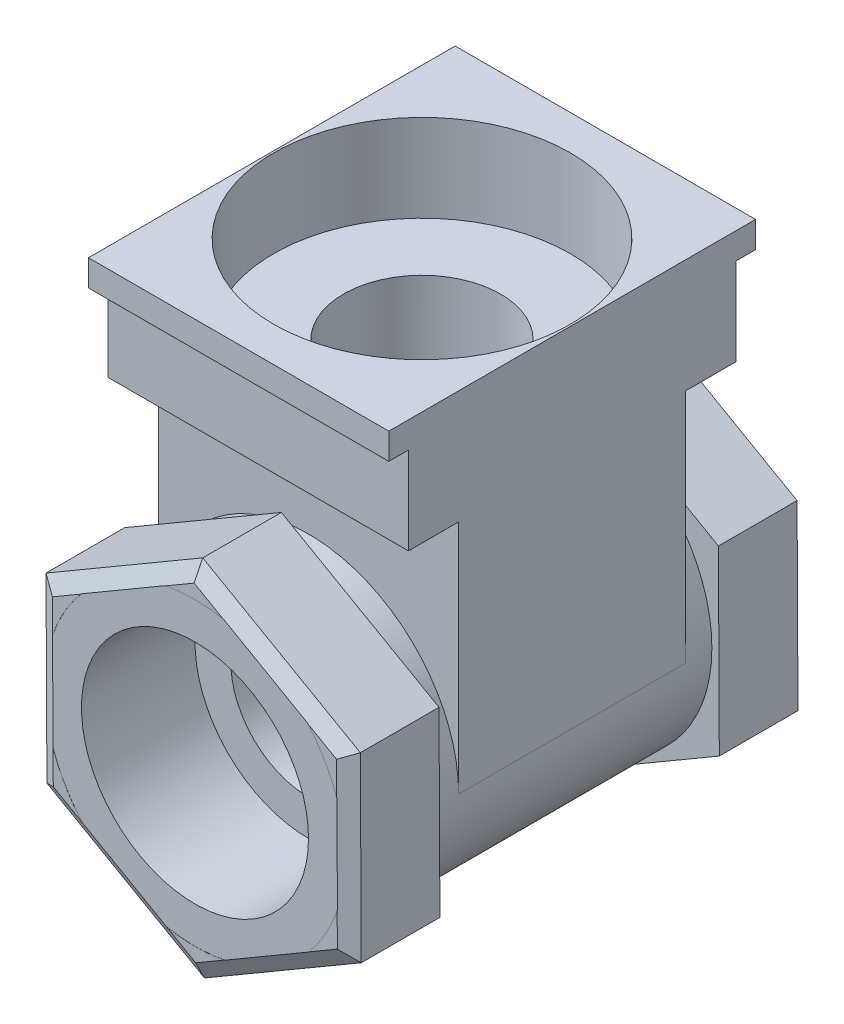
SolidWorks part; units mm, degrees
ref_plane "Front Plane" through (0, 0, 0) normal (0, 0, 1) x (1, 0, 0)
ref_plane "Top Plane" through (0, 0, 0) normal (0, 1, 0) x (1, 0, 0)
ref_plane "Right Plane" through (0, 0, 0) normal (1, 0, 0) x (0, 0, -1)
sketch "Sketch2" plane through (0, 0, 0) normal (0, 0, 1) x (1, 0, 0)
  line L0 (-17.2, 40) -> (17.2, 40)
  line L1 (-17.2, 0) -> (-17.2, 40)
  line L2 (17.2, 0) -> (17.2, 40)
  circle A3 centre (0, 0) radius 17.2
  circle A4 centre (0, 0) radius 12.4222
  circle A5 centre (0, 0) radius 8.5044
  point P7 (0, 40)
  dimension "D1" = 40
extrude "Boss-Extrude2" add sketch "Sketch2" along normal blind 52 contours A3 L2 L0 L1 | A3 A4 | A4 A5
sketch "Sketch4" plane through (0, 0, 0) normal (0, 0, -1) x (-1, 0, 0)
  circle A0 centre (0, 0) radius 13
extrude "Cut-Extrude1" cut sketch "Sketch4" against normal blind 13
sketch "Sketch5" plane through (0, 0, 52) normal (0, 0, 1) x (1, 0, 0)
  circle A0 centre (0, 0) radius 13
extrude "Cut-Extrude2" cut sketch "Sketch5" against normal blind 13
sketch "Sketch6" plane through (0, 0, 39) normal (0, 0, 1) x (1, 0, 0)
  circle A0 centre (0, 0) radius 8.9
extrude "Cut-Extrude3" cut sketch "Sketch6" against normal through all
sketch "Sketch7" plane through (0, 0, 0) normal (0, 0, -1) x (-1, 0, 0)
  line L0 (-17.2, 0) -> (-17.2, 40)
  line L1 (-17.2, 40) -> (17.2, 40)
  line L2 (17.2, 40) -> (17.2, 0)
  arc A1 (-17.2, 0) -> (17.2, 0) centre (0, 0) cw
extrude "Cut-Extrude4" cut sketch "Sketch7" against normal blind 5
sketch "Sketch8" plane through (0, 0, 52) normal (0, 0, 1) x (1, 0, 0)
  line L0 (-17.2, 0) -> (-17.2, 40)
  line L1 (-17.2, 40) -> (17.2, 40)
  line L2 (17.2, 40) -> (17.2, 0)
  arc A0 (-17.2, 0) -> (17.2, 0) centre (0, 0) cw
extrude "Cut-Extrude5" cut sketch "Sketch8" against normal blind 5
sketch "Sketch9" plane through (0, 0, 47) normal (0, 0, 1) x (1, 0, 0)
  line L1 (-17.2, 37) -> (17.2, 37)
  line L2 (-17.2, 40) -> (-17.2, 0) construction
  line L3 (17.2, 0) -> (17.2, 40) construction
  line L4 (-17.2, 37) -> (-17.2, 0)
  line L5 (17.2, 37) -> (17.2, 0)
  arc A0 (-17.2, 0) -> (17.2, 0) centre (0, 0) cw
extrude "Cut-Extrude6" cut sketch "Sketch9" against normal blind 2.25
sketch "Sketch10" plane through (0, 0, 5) normal (0, 0, -1) x (-1, 0, 0)
  line L1 (-17.2, 37) -> (17.2, 37)
  line L2 (-17.2, 40) -> (-17.2, 0) construction
  line L3 (17.2, 0) -> (17.2, 40) construction
  line L4 (-17.2, 37) -> (-17.2, 0)
  line L5 (17.2, 0) -> (17.2, 37)
  arc A0 (-17.2, 0) -> (17.2, 0) centre (0, 0) cw
extrude "Cut-Extrude7" cut sketch "Sketch10" against normal blind 2.25
sketch "Sketch11" plane through (0, 0, 44.75) normal (0, 0, 1) x (1, 0, 0)
  line L1 (-17.2, 27) -> (17.2, 27)
  line L2 (-17.2, 37) -> (-17.2, 0) construction
  line L3 (17.2, 0) -> (17.2, 37) construction
  line L4 (-17.2, 27) -> (-17.2, 0)
  line L5 (17.2, 27) -> (17.2, 0)
  arc A0 (-17.2, 0) -> (17.2, 0) centre (0, 0) cw
extrude "Cut-Extrude9" cut sketch "Sketch11" against normal blind 5.75
sketch "Sketch12" plane through (0, 0, 7.25) normal (0, 0, -1) x (-1, 0, 0)
  line L1 (-17.2, 27) -> (17.2, 27)
  line L2 (-17.2, 37) -> (-17.2, 0) construction
  line L3 (17.2, 0) -> (17.2, 37) construction
  line L4 (-17.2, 27) -> (-17.2, 0)
  line L5 (17.2, 27) -> (17.2, 0)
  arc A0 (-17.2, 0) -> (17.2, 0) centre (0, 0) cw
extrude "Cut-Extrude10" cut sketch "Sketch12" against normal blind 5.75
sketch "Sketch13" plane through (0, 0, 0) normal (0, 0, -1) x (-1, 0, 0)
  line L0 (0, 20.7252) -> (0, 21)
  line L2 (17.948, -10.4819) -> (18.0516, 10.3024)
  line L3 (18.0516, 10.3024) -> (0.1036, 20.7844)
  line L4 (0.1036, 20.7844) -> (-17.948, 10.4819)
  line L5 (-17.948, 10.4819) -> (-18.0516, -10.3024)
  line L6 (-18.0516, -10.3024) -> (-0.1036, -20.7844)
  line L7 (-0.1036, -20.7844) -> (17.948, -10.4819)
  circle A0 centre (0, 0) radius 18 construction
extrude "Boss-Extrude3" add sketch "Sketch13" along normal blind 0.01 and the other way blind 10 contours L6 L7 L2 L3 L4 L5
sketch "Sketch15" plane through (0, 0, 52) normal (0, 0, 1) x (1, 0, 0)
  line L1 (0.1036, -20.7844) -> (18.0516, -10.3024)
  line L2 (18.0516, -10.3024) -> (17.948, 10.4819)
  line L3 (17.948, 10.4819) -> (-0.1036, 20.7844)
  line L4 (-0.1036, 20.7844) -> (-18.0516, 10.3024)
  line L5 (-18.0516, 10.3024) -> (-17.948, -10.4819)
  line L6 (-17.948, -10.4819) -> (0.1036, -20.7844)
  circle A0 centre (0, 0) radius 18 construction
  circle M1 centre (0, 0) radius 17.2
extrude "Boss-Extrude4" add sketch "Sketch15" along normal blind 0.01 and the other way blind 10 contours L5 L6 L1 L2 L3 L4 M1
sketch "Sketch16" plane through (0, 40, 0) normal (0, 1, 0) x (1, 0, 0)
  line L0 (-17.2, -26) -> (17.2, -26)
  line L1 (-17.2, -47) -> (-17.2, -5) construction
  line L2 (17.2, -47) -> (17.2, -5) construction
  line L3 (-0.1036, -4.995) -> (0, -47)
  line L4 (-0.1036, -10) -> (-0.1036, 0.01) construction
  line L5 (17.2, -47) -> (-17.2, -47) construction
  circle A0 centre (0, -26) radius 17
extrude "Cut-Extrude11" cut sketch "Sketch16" against normal blind 10 contours A0
sketch "Sketch17" plane through (0, 30, 0) normal (0, 1, 0) x (1, 0, 0)
  circle A0 centre (0, -26) radius 9
extrude "Cut-Extrude12" cut sketch "Sketch17" against normal blind 40
chamfer "Chamfer3" distance 1 angle 60 12 edges at (-17.9998, -0.0897, -0.01) (-9.0776, 15.5434, -0.01) (-8.9222, -15.6331, -0.01) (9.0776, -15.5434, -0.01) (17.9998, 0.0897, -0.01) (8.9222, 15.6331, -0.01) (8.9222, 15.6331, 52.01) (17.9998, 0.0897, 52.01) (9.0776, -15.5434, 52.01) (-8.9222, -15.6331, 52.01) (-17.9998, -0.0897, 52.01) (-9.0776, 15.5434, 52.01)
